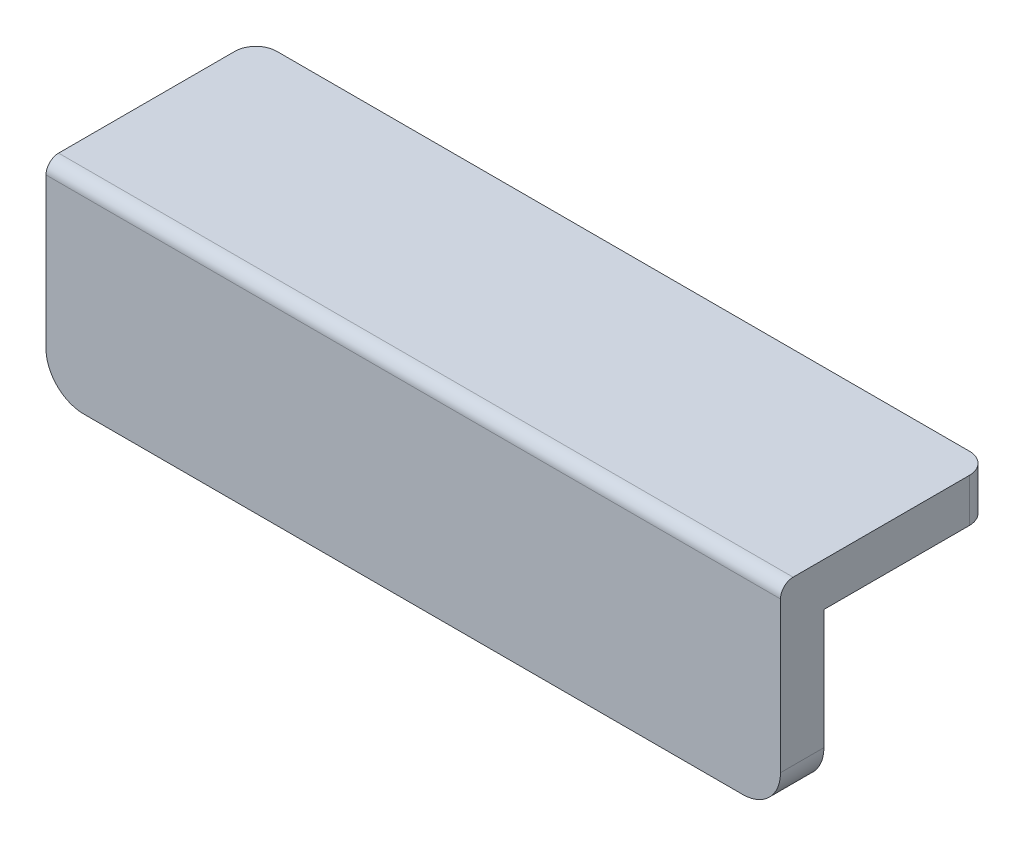
SolidWorks part; units mm, degrees
ref_plane "Front Plane" through (0, 0, 0) normal (0, 0, 1) x (1, 0, 0)
ref_plane "Top Plane" through (0, 0, 0) normal (0, 1, 0) x (1, 0, 0)
ref_plane "Right Plane" through (0, 0, 0) normal (1, 0, 0) x (0, 0, -1)
sketch "Sketch1" plane through (0, 0, 0) normal (0, 0, 1) x (1, 0, 0)
  line L1 (-44.45, -9.525) -> (44.45, -9.525)
  line L2 (-44.45, -9.525) -> (-44.45, 9.525)
  line L3 (-44.45, 9.525) -> (44.45, 9.525)
  line L4 (44.45, -9.525) -> (44.45, 9.525)
  line L5 (-44.45, -9.525) -> (44.45, 9.525) construction
  line L6 (-44.45, 9.525) -> (44.45, -9.525) construction
  point P0 (0, 0)
  dimension "D1" = 19.05
  dimension "D2" = 88.9
extrude "Boss-Extrude1" add sketch "Sketch1" along normal mid plane 5.2578
sketch "Sketch2" plane through (0, 9.525, 0) normal (0, 1, 0) x (1, 0, 0)
  line L0 (44.45, -2.6289) -> (44.45, 2.6289) construction
  line L1 (-44.45, -2.6289) -> (44.45, -2.6289)
  line L2 (-44.45, -2.6289) -> (-44.45, 22.7711)
  line L3 (-44.45, 22.7711) -> (44.45, 22.7711)
  line L4 (44.45, -2.6289) -> (44.45, 22.7711)
  dimension "D1" = 25.4
extrude "Boss-Extrude2" add sketch "Sketch2" along normal blind 5.2578
fillet "Fillet6" radius 4.572 1 edges at (-44.45, -9.525, 0) type face fillet first side face at (0, -9.525, 0) second side face at (-44.45, 6.5151, -9.2689)
fillet "Fillet7" radius 4.572 1 edges at (44.45, -9.525, 0) type face fillet first side face at (2.286, -9.525, 0) second side face at (44.45, 3.3401, -5.9118)
fillet "Fillet8" radius 1.524 1 edges at (0, 14.7828, 2.6289) type face fillet first side face at (0, 14.7828, -10.0711) second side face at (0, -0.214, 2.6289)
fillet "Fillet9" radius 2.54 1 edges at (-44.45, 12.1539, -22.7711) type face fillet first side face at (-44.45, 8.5033, -7.7418) second side face at (0, 12.1539, -22.7711)
fillet "Fillet10" radius 2.54 1 edges at (44.45, 12.1539, -22.7711) type face fillet first side face at (44.45, 6.435, -4.8644) second side face at (1.27, 12.1539, -22.7711)
equation "\"Acrylic\"=\"0.207\""
equation "\"D1@Boss-Extrude1\" = \"Acrylic\""
equation "\"D1@Boss-Extrude2\"=\"Acrylic\""
